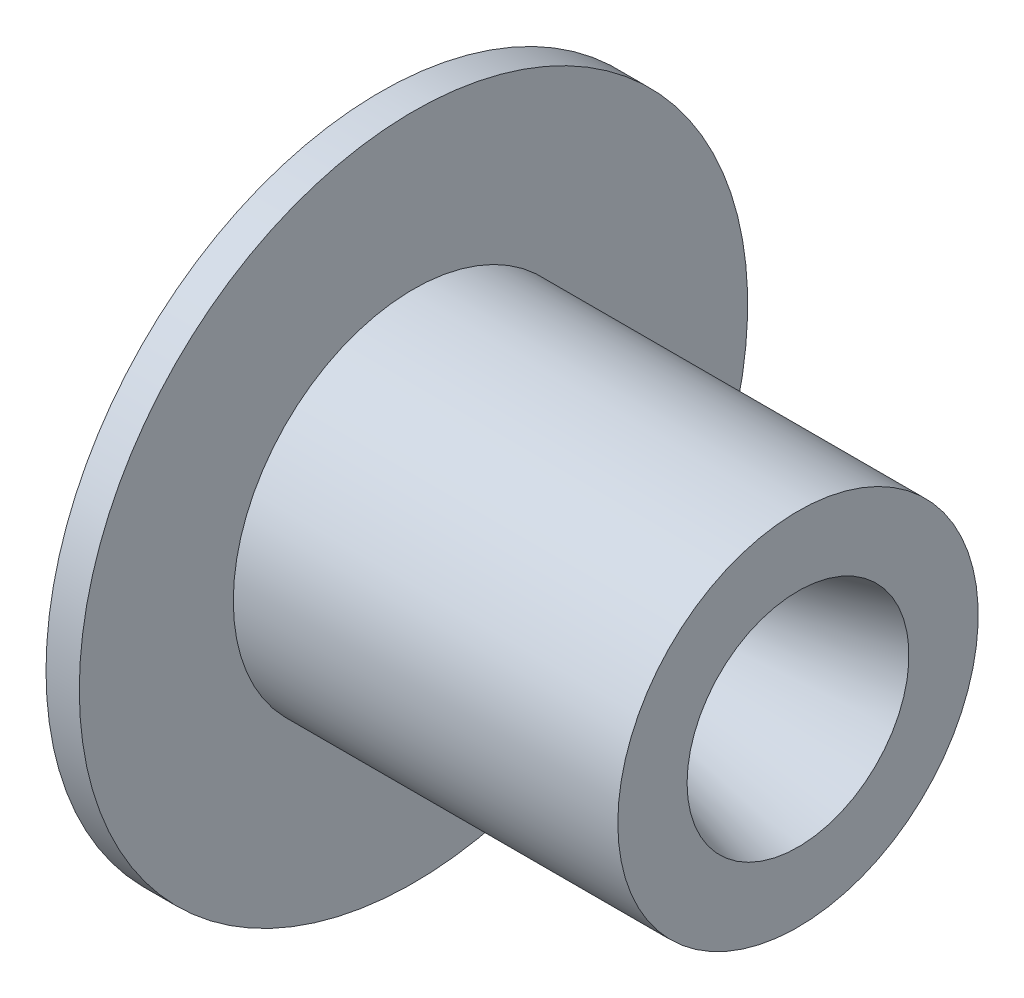
SolidWorks part; units mm, degrees
ref_plane "Front Plane" through (0, 0, 0) normal (0, 0, 1) x (1, 0, 0)
ref_plane "Top Plane" through (0, 0, 0) normal (0, 1, 0) x (1, 0, 0)
ref_plane "Right Plane" through (0, 0, 0) normal (1, 0, 0) x (0, 0, -1)
sketch "Sketch1" plane through (0, 0, 0) normal (0, 0, 1) x (1, 0, 0)
  line L20 (-7.0166, 2.4752) -> (32.997, 2.4752) construction
  line L33 (20, 9.4212) -> (26.5, 9.4212)
  line L34 (20, 9.4212) -> (0, 27.8752)
  line L37 (0, 27.8752) -> (0, 53.4752)
  line L38 (0, 53.4752) -> (5.08, 53.4752)
  line L39 (5.08, 53.4752) -> (5.08, 29.9752)
  line L43 (63.7608, 29.9752) -> (63.7608, 19.4052)
  line L52 (63.7608, 19.4052) -> (26.5, 9.4212)
  line L53 (63.7608, 29.9752) -> (5.08, 29.9752)
  point P0 (-7.0166, 2.4752)
  point P1 (2.54, 53.4752)
  point P12 (20, 9.4212)
  point P24 (26.5, 9.4212)
  dimension "D1" = 6.946
  dimension "D2" = 25.4
  dimension "D5" = 5.08
  dimension "D7" = 20
  dimension "D10" = 15
  dimension "D8" = 16.93
  dimension "D3" = 27.5
  dimension "D4" = 51
  dimension "D6" = 6.5
revolve "Nozzle" add sketch "Sketch1" angle 360 about L20
sketch "Sketch3" plane through (0, 0, 0) normal (-1, 0, 0) x (0, 0, 1)
  circle A0 centre (0, 42.4802) radius 3.3
  circle A1 centre (0, 2.4752) radius 51 construction
  circle A2 centre (28.2878, 30.763) radius 3.3
  circle A3 centre (40.005, 2.4752) radius 3.3
  circle A4 centre (28.2878, -25.8126) radius 3.3
  circle A5 centre (0, -37.5298) radius 3.3
  circle A6 centre (-28.2878, -25.8126) radius 3.3
  circle A7 centre (-40.005, 2.4752) radius 3.3
  circle A8 centre (-28.2878, 30.763) radius 3.3
  circle A13 centre (0, 2.4752) radius 32.6265 construction
  point P6 (0, 2.4752)
  point P29 (0, 2.4752)
  dimension "D1" = 6.6
  dimension "D2" = 40.005
  dimension "D3" = 8
fillet "Rao inlet radius" radius 20.8 1 edges at (26.5, 2.4752, 6.946)
fillet "Rao outlet radius" radius 5.3067 1 edges at (20, 2.4752, 6.946)
sketch "Sketch4" plane through (0, 0, 0) normal (-1, 0, 0) x (0, 0, 1)
  arc A32 (43.1627, 28.069) -> (23.2989, 28.069) centre (33.2308, 25.9282) ccw
  arc A33 (51.0874, 23.8387) -> (44.9363, 26.1653) centre (33.2308, -14.0768) ccw
  arc A51 (21.5254, 26.1653) -> (19.047, 25.36) centre (33.2308, -14.0768) ccw
  arc A69 (43.1627, 28.069) -> (44.9363, 26.1653) centre (45.6457, 28.6042) ccw
  arc A70 (23.2989, 28.069) -> (21.5254, 26.1653) centre (20.816, 28.6042) cw
  arc A72 (70.0553, 8.7019) -> (56.0095, 22.7477) centre (61.5186, 14.211) ccw
  arc A73 (72.6677, 0.107) -> (69.9633, 6.1017) centre (33.2308, -14.0768) ccw
  arc A74 (53.4093, 22.6557) -> (51.0874, 23.8387) centre (33.2308, -14.0768) ccw
  arc A75 (70.0553, 8.7019) -> (69.9633, 6.1017) centre (72.1895, 7.3246) ccw
  arc A76 (56.0095, 22.7477) -> (53.4093, 22.6557) centre (54.6323, 24.8819) cw
  arc A77 (75.3767, -24.0087) -> (75.3767, -4.1449) centre (73.2358, -14.0768) ccw
  arc A78 (71.1464, -31.9334) -> (73.473, -25.7823) centre (33.2308, -14.0768) ccw
  arc A79 (73.473, -2.3714) -> (72.6677, 0.107) centre (33.2308, -14.0768) ccw
  arc A80 (75.3767, -24.0087) -> (73.473, -25.7823) centre (75.9119, -26.4917) ccw
  arc A81 (75.3767, -4.1449) -> (73.473, -2.3714) centre (75.9119, -1.662) cw
  arc A82 (56.0095, -50.9014) -> (70.0553, -36.8555) centre (61.5186, -42.3646) ccw
  arc A83 (47.4147, -53.5137) -> (53.4093, -50.8093) centre (33.2308, -14.0768) ccw
  arc A84 (69.9633, -34.2553) -> (71.1464, -31.9334) centre (33.2308, -14.0768) ccw
  arc A85 (56.0095, -50.9014) -> (53.4093, -50.8093) centre (54.6323, -53.0355) ccw
  arc A86 (70.0553, -36.8555) -> (69.9633, -34.2553) centre (72.1895, -35.4783) cw
  arc A87 (23.2989, -56.2227) -> (43.1627, -56.2227) centre (33.2308, -54.0818) ccw
  arc A88 (19.047, -53.5137) -> (21.5254, -54.319) centre (33.2308, -14.0768) ccw
  arc A89 (44.9363, -54.319) -> (47.4147, -53.5137) centre (33.2308, -14.0768) ccw
  arc A90 (23.2989, -56.2227) -> (21.5254, -54.319) centre (20.816, -56.7579) ccw
  arc A91 (43.1627, -56.2227) -> (44.9363, -54.319) centre (45.6457, -56.7579) cw
  arc A92 (-3.5937, -36.8555) -> (10.4521, -50.9014) centre (4.943, -42.3646) ccw
  arc A93 (-4.6847, -31.9334) -> (-3.5017, -34.2553) centre (33.2308, -14.0768) ccw
  arc A94 (13.0523, -50.8093) -> (19.047, -53.5137) centre (33.2308, -14.0768) ccw
  arc A95 (-3.5937, -36.8555) -> (-3.5017, -34.2553) centre (-5.7279, -35.4783) ccw
  arc A96 (10.4521, -50.9014) -> (13.0523, -50.8093) centre (11.8294, -53.0355) cw
  arc A97 (-8.915, -4.1449) -> (-8.915, -24.0087) centre (-6.7742, -14.0768) ccw
  arc A98 (-6.206, 0.107) -> (-7.0113, -2.3714) centre (33.2308, -14.0768) ccw
  arc A99 (-7.0113, -25.7823) -> (-4.6847, -31.9334) centre (33.2308, -14.0768) ccw
  arc A100 (-8.915, -4.1449) -> (-7.0113, -2.3714) centre (-9.4502, -1.662) ccw
  arc A101 (-8.915, -24.0087) -> (-7.0113, -25.7823) centre (-9.4502, -26.4917) cw
  arc A102 (10.4521, 22.7477) -> (-3.5937, 8.7019) centre (4.943, 14.211) ccw
  arc A103 (19.047, 25.36) -> (13.0523, 22.6557) centre (33.2308, -14.0768) ccw
  arc A104 (-3.5017, 6.1017) -> (-6.206, 0.107) centre (33.2308, -14.0768) ccw
  arc A105 (10.4521, 22.7477) -> (13.0523, 22.6557) centre (11.8294, 24.8819) ccw
  arc A106 (-3.5937, 8.7019) -> (-3.5017, 6.1017) centre (-5.7279, 7.3246) cw
  point P1 (33.2308, -14.0768)
  point P69 (33.2308, -14.0768)
  point P78 (23.0923, 26.5884)
  dimension "D1" = 8
  dimension "D3" = 41.91
  dimension "D4" = 2.54
  dimension "D2" = 10.16
  dimension "D5" = 40.005
equation "\"radius\"= 1in"
equation "\"Flange\"= 2.35cm"
equation "\"Length\"= 2cm"
equation "\"Flange_Thickness\"= 0.2in"
equation "\"offset\"= 0.625cm"
equation "\"D2@Sketch1\"=\"radius\""
equation "\"throat\"= 0.6946cm"
equation "\"hole_dia\"= 0.66cm"
equation "\"D1@Sketch1\"=\"throat\""
equation "\"D5@Sketch1\"=\"Flange_Thickness\""
equation "\"D7@Sketch1\"=\"Length\""
equation "\"D1@Sketch3\"=\"hole_dia\""
equation "\"D2@Sketch3\"=1.575in"
equation "\"Seal_dia\"= 2.5cm"
equation "\"Seal_depth\"= 0.1cm"
equation "\"Seal_width\"= 0.15cm"
equation "\"Nozzle_angle\"= 15"
equation "\"D10@Sketch1\"=\"Nozzle_angle\""
equation "\"nozzle_length\"= 6.34"
equation "\"bolt_head_dia\"=2.3795"
equation "\"bolt_rad\"= \"radius\" + 0.5 * \"Flange\" + ( ( \"offset\" ^ 2 ) - ( \"Flange_Thickness\" ^ 2 ) ) ^ 0.5cm"
equation "\"scallop_inner_dia\"= 3.3in"
equation "\"exit_rad\"= 1.693cm"
equation "\"D8@Sketch1\"=\"exit_rad\""
equation "\"outside_dia\"= 2.75cm"
equation "\"D3@Sketch1\"=\"outside_dia\""
equation "\"D4@Sketch1\"=\"outside_dia\"+\"Flange\""
equation "\"Scallop_OD\"= 0.8in"
equation "\"D1@Rao outlet radius\" = 2 * 0.382 * \"throat\""
equation "\"D3@Sketch5\"=\"Scallop_OD\"/2"
equation "\"D4@Sketch5\"=\"scallop_inner_dia\"/2"
